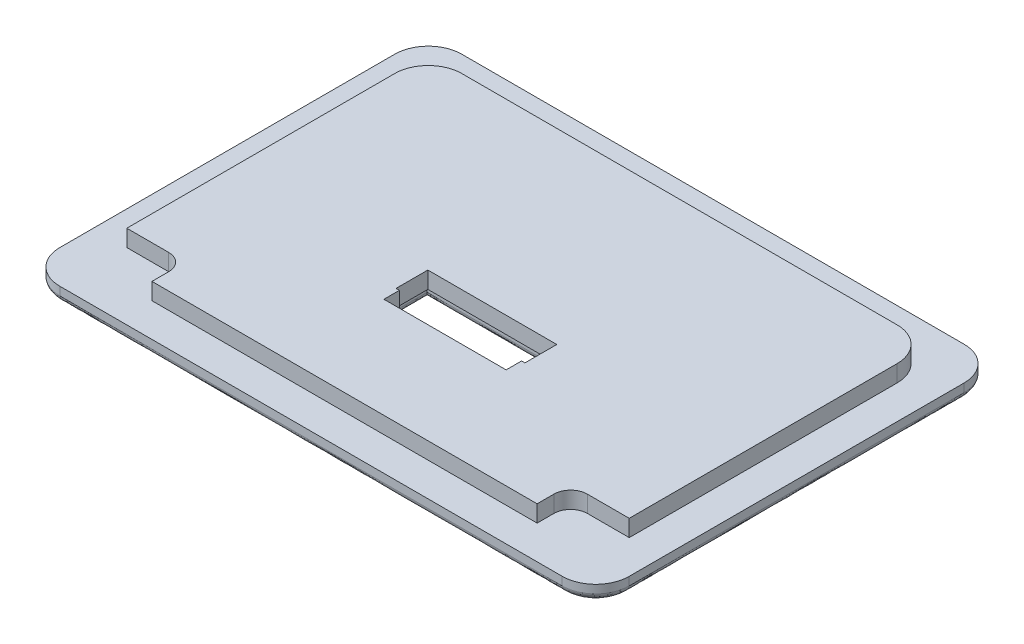
SolidWorks part; units mm, degrees
ref_plane "Front Plane" through (0, 0, 0) normal (0, 0, 1) x (1, 0, 0)
ref_plane "Top Plane" through (0, 0, 0) normal (0, 1, 0) x (1, 0, 0)
ref_plane "Right Plane" through (0, 0, 0) normal (1, 0, 0) x (0, 0, -1)
sketch "Sketch3" plane through (0, 0, 0) normal (0, 1, 0) x (1, 0, 0)
  line L0 (-11.5, -10) -> (11.5, -10)
  line L1 (-15, -8) -> (-15, 8)
  line L2 (-13, 10) -> (13, 10)
  line L3 (15, -8) -> (15, 8)
  line L4 (-15, 10) -> (15, -10) construction
  line L5 (-15, -12) -> (15, -12)
  line L6 (-17, -10) -> (-17, 10)
  line L7 (-15, 12) -> (15, 12)
  line L8 (17, -10) -> (17, 10)
  line L9 (-17, 12) -> (17, -12) construction
  line L10 (0, 12) -> (0, -10) construction
  line L15 (-15, 0) -> (15, 0) construction
  line L16 (-11.5, -9) -> (-11.5, -10)
  line L17 (-15, -8) -> (-12.5, -8)
  line L20 (11.5, -9) -> (11.5, -10)
  line L21 (15, -8) -> (12.5, -8)
  arc A2 (17, -10) -> (15, -12) centre (15, -10) cw
  arc A3 (-17, -10) -> (-15, -12) centre (-15, -10) ccw
  arc A4 (15, 12) -> (17, 10) centre (15, 10) cw
  arc A5 (-15, 12) -> (-17, 10) centre (-15, 10) ccw
  arc A6 (-13, 10) -> (-15, 8) centre (-13, 8) ccw
  arc A7 (13, 10) -> (15, 8) centre (13, 8) cw
  arc A9 (-12.5, -8) -> (-11.5, -9) centre (-12.5, -9) cw
  arc A10 (12.5, -8) -> (11.5, -9) centre (12.5, -9) ccw
  point P0 (0, 0)
  point P16 (0, 0)
  point P17 (-12, 9.5)
  dimension "D2" = 2
  dimension "D7" = 2
  dimension "D3" = 30
  dimension "D4" = 34
  dimension "D5" = 24
  dimension "D6" = 20
sketch "Sketch4" plane through (0, 0, 0) normal (0, 1, 0) x (1, 0, 0)
  line L0 (-11.5, -10) -> (11.5, -10)
  line L1 (-15, -8) -> (-15, 8)
  line L2 (-13, 10) -> (13, 10)
  line L3 (15, -8) -> (15, 8)
  line L4 (-11.5, -9) -> (-11.5, -10)
  line L5 (-15, -8) -> (-12.5, -8)
  line L6 (11.5, -9) -> (11.5, -10)
  line L7 (15, -8) -> (12.5, -8)
  arc A0 (-13, 10) -> (-15, 8) centre (-13, 8) ccw
  arc A1 (13, 10) -> (15, 8) centre (13, 8) cw
  arc A2 (-12.5, -8) -> (-11.5, -9) centre (-12.5, -9) cw
  arc A3 (12.5, -8) -> (11.5, -9) centre (12.5, -9) ccw
extrude "Boss-Extrude1" add sketch "Sketch4" along normal blind 2
extrude "Boss-Extrude2" add sketch "Sketch3" along normal blind 1 contours L8 A4 L7 A5 L6 A3 L5 A2
sketch "Sketch5" plane through (0, 2, 0) normal (0, 1, 0) x (1, 0, 0)
  line L0 (-13.4265, -4) -> (12.9043, -4) construction
  line L1 (-11.5, -10) -> (11.5, -10) construction
  line L2 (-15, -12) -> (15, -12) construction
  line L3 (-3.65, -4) -> (3.65, -4)
  line L4 (-3.85, -1.1748) -> (3.85, -1.1748)
  line L5 (-3.65, -4) -> (-3.65, -3.0769)
  line L6 (-3.85, -1.1748) -> (-3.85, -3.0769)
  line L7 (-3.85, -3.0769) -> (-3.65, -3.0769)
  line L8 (0, 10) -> (0, -10) construction
  line L9 (-13, 10) -> (13, 10) construction
  line L10 (11.5, -10) -> (-11.5, -10) construction
  line L11 (3.85, -3.0769) -> (3.65, -3.0769)
  line L12 (3.85, -1.1748) -> (3.85, -3.0769)
  line L13 (3.65, -4) -> (3.65, -3.0769)
  point P8 (0, -4)
  point P9 (0, -10)
  point P13 (0, -1.1748)
  dimension "D1" = 6
  dimension "D2" = 7.3
  dimension "D3" = 7.7
extrude "Cut-Extrude1" cut sketch "Sketch5" against normal through all
sketch "Sketch7" plane through (0, 0, 0) normal (0, -1, 0) x (1, 0, 0)
  line L0 (-4.2193, 3.3748) -> (-3.9224, 3.3748)
  line L6 (0, 11.8852) -> (0, -9.5356) construction
  line L10 (3.9224, 4.3043) -> (3.9224, 3.3748)
  line L11 (4.2193, 0.8446) -> (4.2193, 3.3748)
  line L12 (4.2193, 3.3748) -> (3.9224, 3.3748)
  line L16 (-4.2193, 0.8446) -> (4.2193, 0.8446)
  line L17 (-3.9224, 4.3043) -> (3.9224, 4.3043)
  line L18 (-15, 12) -> (15, 12) construction
  line L19 (0, 12) -> (0, -12) construction
  line L20 (-15, -12) -> (15, -12) construction
  line L21 (-4.2193, 0.8446) -> (-4.2193, 3.3748)
  line L22 (-3.9224, 4.3043) -> (-3.9224, 3.3748)
  point P10 (0, 0.8446)
  point P12 (0, 4.3043)
extrude "Cut-Extrude2" cut sketch "Sketch7" against normal blind 1
fillet "Fillet2" radius 0.5 16 edges at (17, 0, 0) (16.4142, 0, -11.4142) (0, 0, -12) (-16.4142, 0, -11.4142) (-17, 0, 0) (-16.4142, 0, 11.4142) (0, 0, 12) (16.4142, 0, 11.4142) (4.2193, 0, 2.1097) (4.0708, 0, 3.3748) (3.9224, 0, 3.8396) (0, 0, 4.3043) (-3.9224, 0, 3.8396) (-4.0708, 0, 3.3748) (-4.2193, 0, 2.1097) (0, 0, 0.8446) conic radius 1
